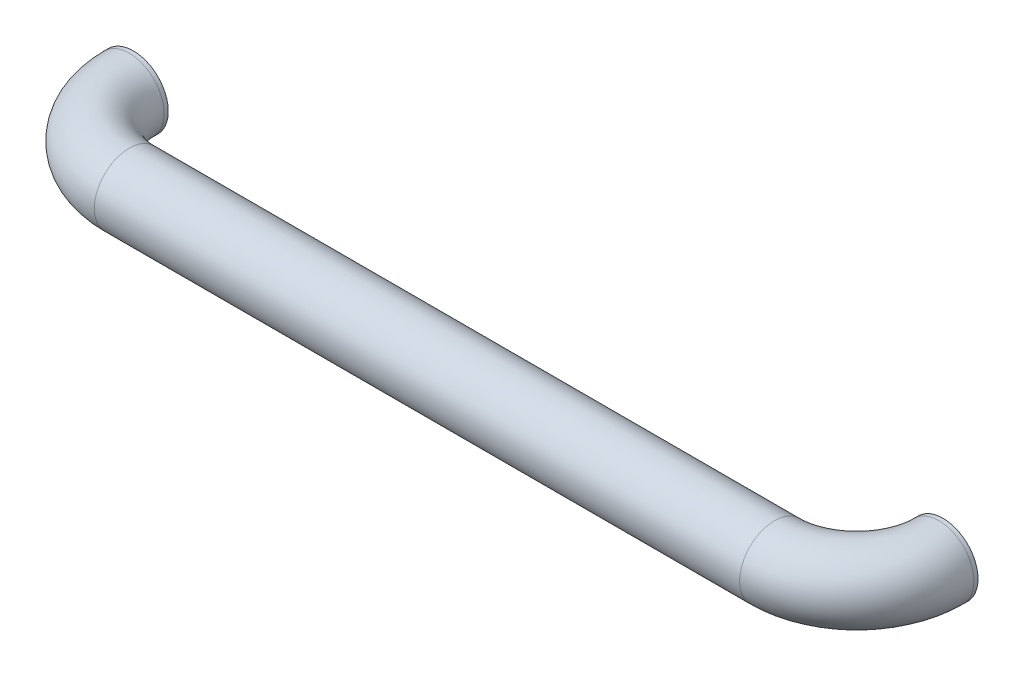
SolidWorks part; units mm, degrees
ref_plane "前视基准面" through (0, 0, 0) normal (0, 0, 1) x (1, 0, 0)
ref_plane "上视基准面" through (0, 0, 0) normal (0, 1, 0) x (1, 0, 0)
ref_plane "右视基准面" through (0, 0, 0) normal (1, 0, 0) x (0, 0, -1)
other "Configuration Table"
sketch "草图1" plane through (0, 0, 0) normal (0, 1, 0) x (1, 0, 0)
  line L0 (0, 0) -> (0, 46.7607) construction
  line L1 (-78.5, 0) -> (78.5, 0)
  arc A0 (78.5, 0) -> (98.5, 20) centre (78.5, 20) ccw
  arc A1 (-78.5, 0) -> (-98.5, 20) centre (-78.5, 20) cw
  point P8 (81.2326, 1.3864)
  point P10 (98.5, 20)
  dimension "D2" = 20
  dimension "D1" = 98.5
sketch "草图2" plane through (0, 0, 0) normal (1, 0, 0) x (0, 0, -1)
  circle A0 centre (0, 0) radius 8.5
  circle A1 centre (0, 0) radius 8
  dimension "D1" = 17
  dimension "D2" = 16
sweep "扫描1" add profiles "草图2" path "草图1"
sketch "草图5" plane through (0, 0, -20) normal (0, 0, -1) x (-1, 0, 0)
  circle A0 centre (-98.5, 0) radius 8.5
  circle A1 centre (98.5, 0) radius 8.5
  circle A2 centre (-98.5, 0) radius 2.1
  circle A3 centre (98.5, 0) radius 2.1
  dimension "D1" = 4.2
  dimension "D2" = 4.2
extrude "凸台-拉伸1" add sketch "草图5" along normal blind 1
